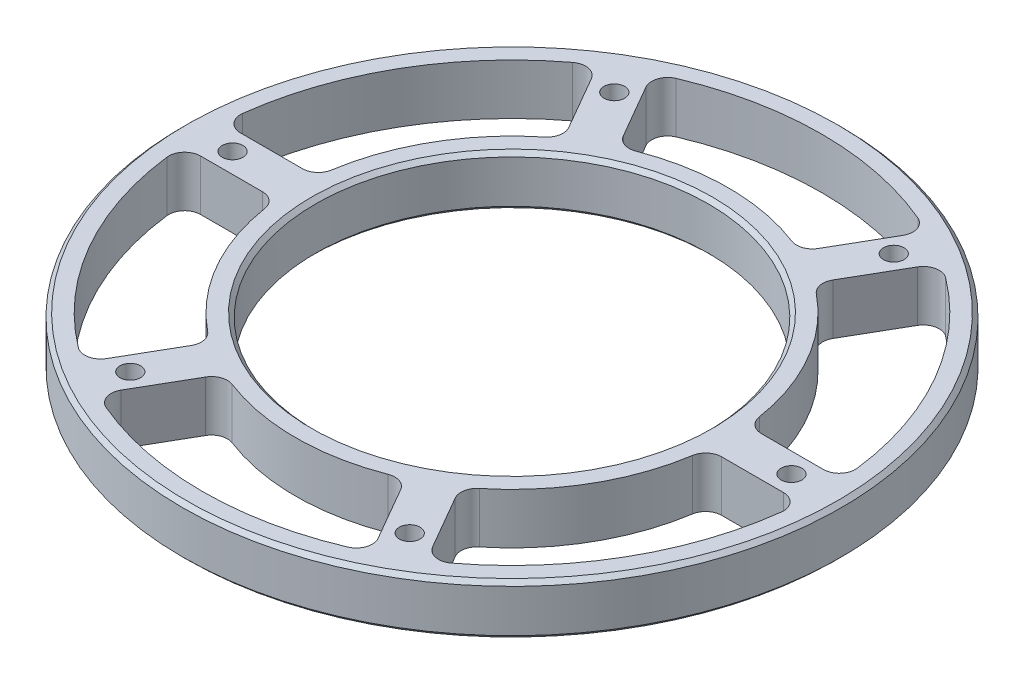
SolidWorks part; units mm, degrees
material "6061-T6 (SS)"
ref_plane "Front Plane" through (0, 0, 0) normal (0, 0, 1) x (1, 0, 0)
ref_plane "Top Plane" through (0, 0, 0) normal (0, 1, 0) x (1, 0, 0)
ref_plane "Right Plane" through (0, 0, 0) normal (1, 0, 0) x (0, 0, -1)
sketch "Sketch2" plane through (0, 0, 0) normal (1, 0, 0) x (0, 0, -1)
  line L0 (-49.2125, 0) -> (-82.55, 0)
  line L1 (-82.55, 0) -> (-82.55, 12.7)
  line L2 (-82.55, 12.7) -> (-49.2125, 12.7)
  line L3 (-49.2125, 12.7) -> (-49.2125, 0)
  dimension "D1" = 82.55
  dimension "D2" = 12.7
  dimension "D4" = 49.2125
ref_axis "Axis1" through (0, -0.635, 0) along (0, 1, 0)
revolve "Revolve1" add sketch "Sketch2" angle 360 about axis through (0, -0.635, 0) along (0, 1, 0)
hole_wizard "#6 (0.204) Diameter Hole1" positions "Sketch6" profile "Sketch7" hole size "#6" standard "ANSI Inch" end condition through all
sketch "Sketch6" plane through (0, 12.7, 0) normal (0, 1, 0) x (1, 0, 0)
  line L0 (0, 0) -> (-69.8201, 120.932) construction
  line L2 (0, 0) -> (0, 109.0908) construction
  point P0 (-35, 60.6218)
  dimension "D1" = 30
  dimension "D2" = 70
sketch "Sketch7" plane through (-35, 12.7, -60.6218) normal (1, 0, 0) x (0, 0, 1)
  line L0 (0, 0) -> (0, 12.7)
  line L1 (0, 12.7) -> (2.5908, 12.7)
  line L2 (2.5908, 12.7) -> (2.5908, 0)
  line L5 (2.5908, 0) -> (0, 0)
  line L11 (0, -6.35) -> (0, 107.95) construction
  dimension "Thru Hole Dia." = 5.1816
  dimension "Thru Hole Depth" = 12.7
pattern_circular "CirPattern3" count 6 over 360 about axis through (0, -0.635, 0) along (0, 1, 0) of "#6 (0.204) Diameter Hole1"
sketch "Sketch8" plane through (0, 12.7, 0) normal (0, 1, 0) x (1, 0, 0)
  line L4 (0, 0) -> (0, 93.9995) construction
  line L5 (-22.6606, 49.2493) -> (-34.3642, 69.5205)
  line L6 (22.6606, 49.2493) -> (34.3642, 69.5205)
  line L7 (0, 0) -> (-35, 60.6218) construction
  arc A0 (-22.6606, 49.2493) -> (22.6606, 49.2493) centre (0, 0) cw
  arc A1 (-34.3642, 69.5205) -> (34.3642, 69.5205) centre (0, 0) cw
  circle A2 centre (0, 0) radius 82.55 construction
  circle A4 centre (0, 0) radius 49.2125 construction
  dimension "D1" = 5
  dimension "D2" = 5
  dimension "D3" = 5
extrude "Cut-Extrude1" cut sketch "Sketch8" against normal through all
fillet "Fillet1" radius 4 4 edges at (-22.6606, 6.35, -49.2493) (22.6606, 6.35, -49.2493) (34.3642, 6.35, -69.5205) (-34.3642, 6.35, -69.5205)
pattern_circular "CirPattern4" count 6 over 360 about axis through (0, -0.635, 0) along (0, 1, 0) of "Cut-Extrude1", "Fillet1"
chamfer "Chamfer1" distance 1 angle 45 2 edges at (0, 12.7, -49.2125) (0, 0, -49.2125)
chamfer "Chamfer2" distance 1 angle 45 2 edges at (0, 12.7, -82.55) (0, 0, -82.55)
equation "\"TubeDiameter\" = 6.500in"
equation "\"D1@Sketch2\"=\"TubeDiameter\"/2"
